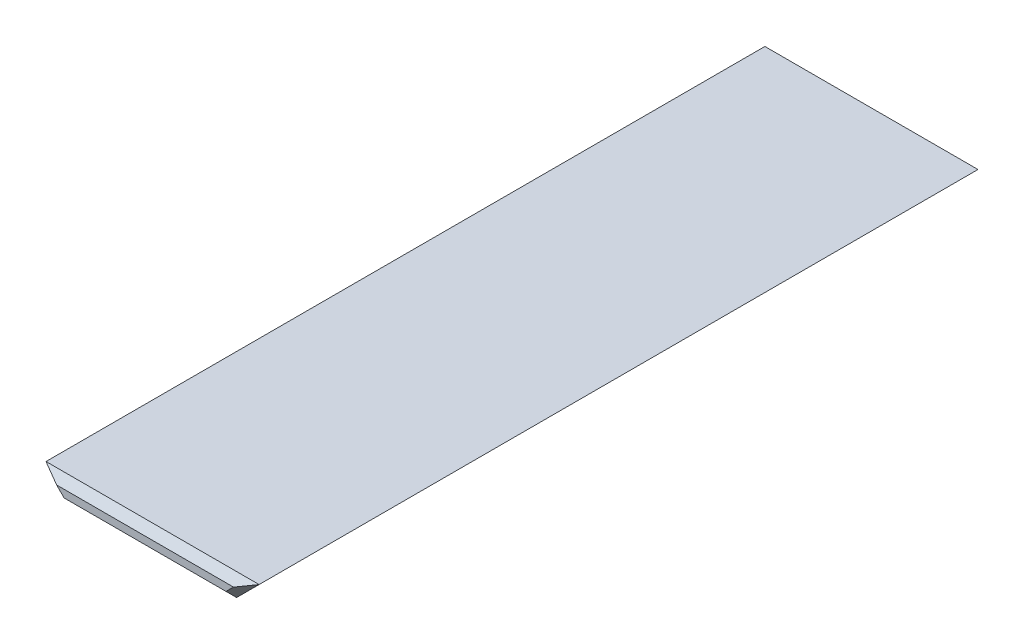
SolidWorks part; units mm, degrees
ref_plane "Plan de face" through (0, 0, 0) normal (0, 0, 1) x (1, 0, 0)
ref_plane "Plan de dessus" through (0, 0, 0) normal (0, 1, 0) x (1, 0, 0)
ref_plane "Plan de droite" through (0, 0, 0) normal (1, 0, 0) x (0, 0, -1)
sketch "Esquisse1" plane through (0, 0, 0) normal (0, 0, 1) x (1, 0, 0)
  line L0 (-11.2, 0) -> (11.2, 0)
  line L1 (11.2, 0) -> (14.2, 3)
  line L2 (14.2, 3) -> (-14.2, 3)
  line L3 (0, 0) -> (0, 3) construction
  line L4 (-11.2, 0) -> (-14.2, 3)
  dimension "D1" = 45
  dimension "D2" = 14.2
  dimension "D3" = 3
extrude "Boss.-Extru.1" add sketch "Esquisse1" along normal blind 96.8
chamfer "Chanfrein1" distance 1 angle 45 4 edges at (0, 0, 96.8) (-12.7, 1.5, 96.8) (0, 3, 96.8) (12.7, 1.5, 96.8)
chamfer "Chanfrein2" distance 3 angle 45 1 edges at (0, 0, 0)
